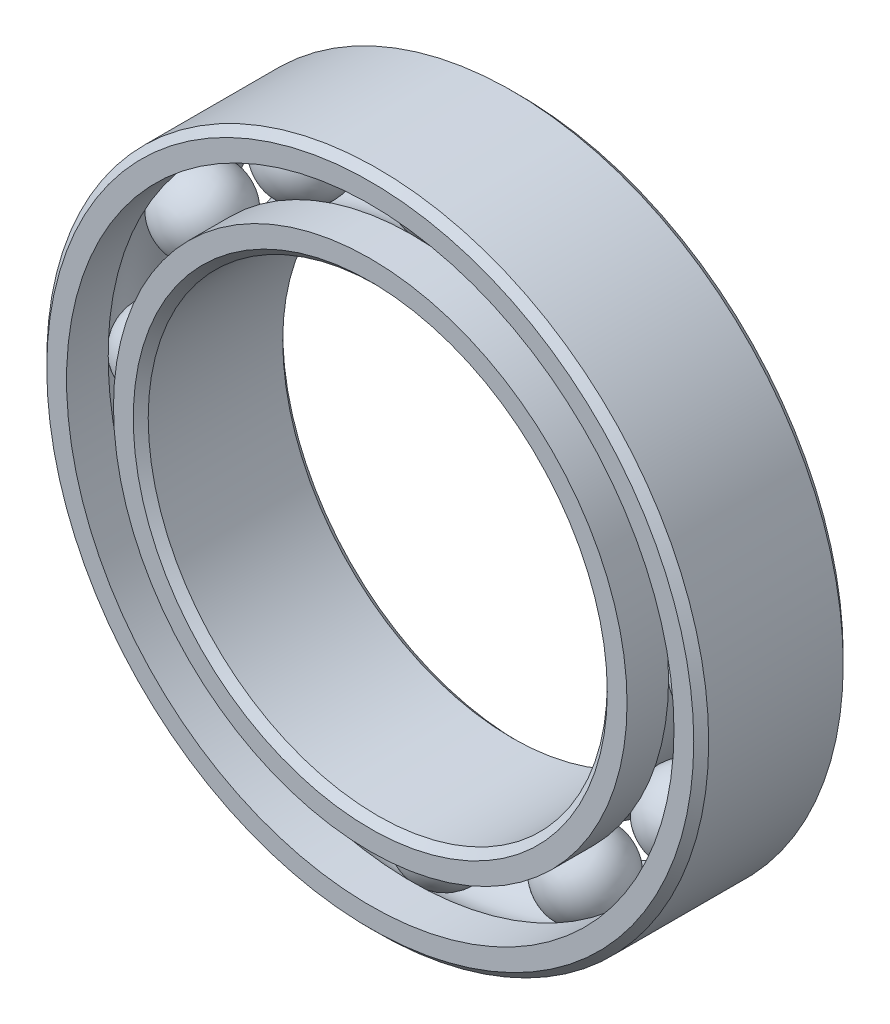
SolidWorks part; units mm, degrees
ref_plane "Front Plane" through (0, 0, 0) normal (0, 0, 1) x (1, 0, 0)
ref_plane "Top Plane" through (0, 0, 0) normal (0, 1, 0) x (1, 0, 0)
ref_plane "Right Plane" through (0, 0, 0) normal (1, 0, 0) x (0, 0, -1)
sketch "Sketch1" plane through (0, 0, 0) normal (1, 0, 0) x (0, 0, -1)
  line L0 (-3.5, 0) -> (3.5, 0) construction
  line L1 (0, 15.5) -> (0, -15.5) construction
  line L2 (3.15, 15.5) -> (-3.15, 15.5)
  line L3 (-3.15, 15.5) -> (-3.5, 15.15)
  line L4 (-3.5, 15.15) -> (-3.5, 14.2239)
  line L5 (-3.5, 14.2239) -> (-1.5556, 14.2239)
  line L6 (3.5, 14.2239) -> (1.5556, 14.2239)
  line L7 (3.5, 15.15) -> (3.5, 14.2239)
  line L8 (3.15, 15.5) -> (3.5, 15.15)
  line L9 (0, 15.5) -> (0, 13.125) construction
  line L10 (0, 13.125) -> (0, 10.75) construction
  arc A0 (-1.5556, 14.2239) -> (1.5556, 14.2239) centre (0, 13.125) cw
  point P14 (0, 10.75)
  dimension "Width" = 7
  dimension "OD" = 31
  dimension "D1" = 45
  dimension "D2" = 0.35
  dimension "Shaft Dia" = 21.5
  dimension "D3" = 3.1111
  dimension "D4" = 1.0989
revolve "Revolve1" add sketch "Sketch1" angle 360 about L0
sketch "Sketch3" plane through (0, 0, 0) normal (1, 0, 0) x (0, 0, -1)
  line L0 (-3.5, 12.0261) -> (-1.5556, 12.0261)
  line L1 (0, 15.5) -> (0, -15.5) construction
  line L2 (-3.5, 15.15) -> (-3.5, 14.2239) construction
  line L3 (-3.5, 12.0261) -> (-3.5, 11.1)
  line L4 (-3.15, 15.5) -> (-3.5, 15.15) construction
  line L5 (-3.5, 11.1) -> (-3.15, 10.75)
  line L6 (-3.15, 10.75) -> (3.15, 10.75)
  line L7 (3.15, 15.5) -> (3.15, -15.5) construction
  line L8 (3.15, 10.75) -> (3.5, 11.1)
  line L9 (3.5, -15.15) -> (3.5, 15.15) construction
  line L10 (3.5, 11.1) -> (3.5, 12.0261)
  line L11 (3.5, 12.0261) -> (1.5556, 12.0261)
  line L13 (3.15, 15.5) -> (3.5, 15.15) construction
  arc A0 (1.5556, 14.2239) -> (-1.5556, 14.2239) centre (0, 13.125) ccw construction
  arc A1 (1.5556, 12.0261) -> (-1.5556, 12.0261) centre (0, 13.125) cw
revolve "Revolve3" add sketch "Sketch3" angle 360 about L0
sketch "Sketch4" plane through (0, 0, 0) normal (1, 0, 0) x (0, 0, -1)
  line L0 (-1.9046, 13.125) -> (1.9046, 13.125)
  arc A2 (-1.9046, 13.125) -> (1.9046, 13.125) centre (0, 13.125) cw
  arc A3 (1.5556, 14.2239) -> (-1.5556, 14.2239) centre (0, 13.125) ccw construction
revolve "Revolve4" add sketch "Sketch4" angle 360 about L0
ref_axis "Axis1" through (0, 0, -3.5) along (0, 0, 1)
pattern_circular "CirPattern1" count 12 every 30 about axis through (0, 0, -3.5) along (0, 0, 1) of bodies 104
sketch "Sketch5" plane through (0, 0, 0) normal (1, 0, 0) x (0, 0, -1)
  line L0 (-3.5, 14.2239) -> (-1.5556, 14.2239) construction
  line L1 (-3.325, 14.2239) -> (-1.9046, 14.2239)
  line L2 (-3.325, 14.2239) -> (-3.325, 12.0261)
  line L3 (-3.325, 12.0261) -> (-1.9046, 12.0261)
  line L4 (-1.9046, 14.2239) -> (-1.9046, 12.0261)
  line L5 (-3.5, 12.0261) -> (-1.5556, 12.0261) construction
  line L6 (3.5, 14.2239) -> (1.5556, 14.2239) construction
  line L7 (3.325, 14.2239) -> (1.9046, 14.2239)
  line L8 (3.325, 14.2239) -> (3.325, 12.0261)
  line L9 (3.325, 12.0261) -> (1.9046, 12.0261)
  line L10 (1.9046, 14.2239) -> (1.9046, 12.0261)
  line L11 (3.5, 12.0261) -> (1.5556, 12.0261) construction
  line L12 (-3.15, 15.5) -> (-3.5, 15.15) construction
  point P18 (-3.325, 15.325)
equation "\"D2@Sketch1\" = \"Width@Sketch1\"*.05"
equation "\"D3@Sketch1\" = \"Width@Sketch1\"/2.25"
equation "\"D4@Sketch1\" = (((\"OD@Sketch1\"-\"Width@Sketch1\")/2)/3.25)/3.5"
equation "\"D2@CirPattern1\" = 360/\"Balls@CirPattern1\""
